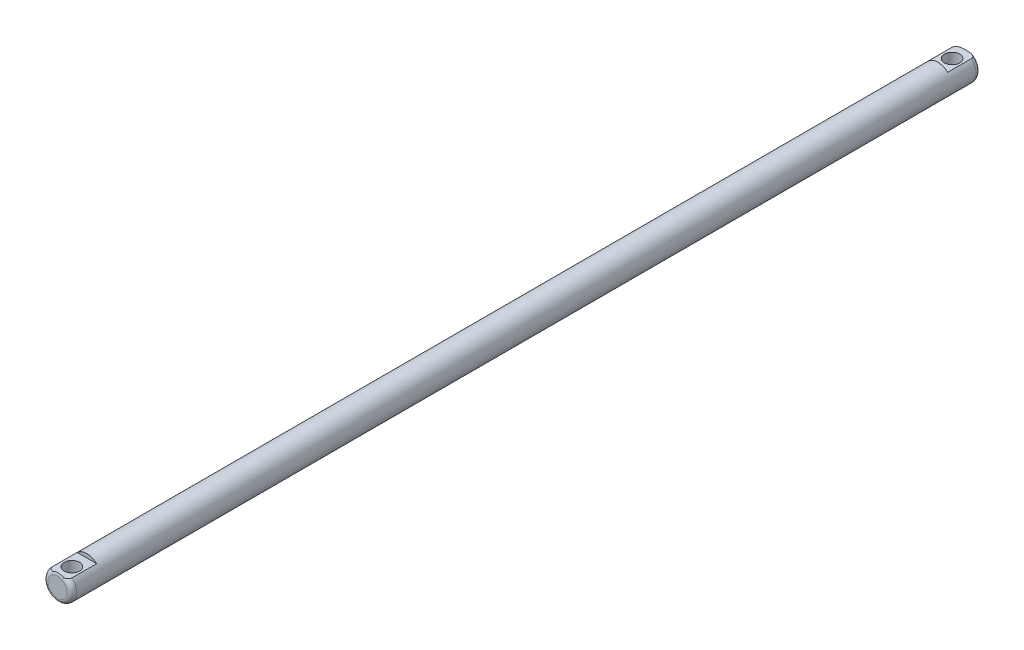
SolidWorks part; units mm, degrees
ref_plane "Front Plane" through (0, 0, 0) normal (0, 0, 1) x (1, 0, 0)
ref_plane "Top Plane" through (0, 0, 0) normal (0, 1, 0) x (1, 0, 0)
ref_plane "Right Plane" through (0, 0, 0) normal (1, 0, 0) x (0, 0, -1)
sketch "Sketch1" plane through (0, 0, 0) normal (0, 0, 1) x (1, 0, 0)
  circle A0 centre (-5.9113, 0) radius 1.5
extrude "Boss-Extrude1" add sketch "Sketch1" along normal blind 95
sketch "Sketch3" plane through (0, 0, 0) normal (0, 1, 0) x (1, 0, 0)
  line L0 (-4.4113, 0) -> (-7.4113, 0) construction
  line L1 (-7.4113, 0) -> (-7.4113, -95) construction
  line L2 (-7.4113, -95) -> (-4.4113, -95) construction
  circle A0 centre (-5.9113, -1.5) radius 0.8
  circle A1 centre (-5.9113, -93.5) radius 0.8
  dimension "D1" = 1.6
  dimension "D4" = 1.5
  dimension "D5" = 1.6
  dimension "D2" = 1.5
  dimension "D3" = 1.5
  dimension "D6" = 1.5
extrude "Cut-Extrude1" cut sketch "Sketch3" against normal blind 50 and the other way blind 50
fillet "Fillet1" radius 0.5 2 edges at (-4.4113, 0, 0) (-4.4113, 0, 95)
ref_plane "Plane1" through (0, 1.5, 0) normal (0, 1, 0) x (1, 0, 0)
sketch "Sketch4" plane through (0, 1.5, 0) normal (0, 1, 0) x (1, 0, 0)
  line L0 (-4.4113, -94.5) -> (-4.4113, -0.5) construction
  line L1 (-7.1613, -91.933) -> (-4.6613, -91.933)
  line L2 (-7.1613, -91.933) -> (-7.1613, -94.933)
  line L3 (-7.1613, -94.933) -> (-4.6613, -94.933)
  line L4 (-4.6613, -91.933) -> (-4.6613, -94.933)
  line L5 (-7.1613, 0.0158) -> (-4.6613, 0.0158)
  line L6 (-7.1613, 0.0158) -> (-7.1613, -2.9842)
  line L7 (-7.1613, -2.9842) -> (-4.6613, -2.9842)
  line L8 (-4.6613, 0.0158) -> (-4.6613, -2.9842)
  arc A0 (-4.9113, -95) -> (-4.4113, -94.5) centre (-4.9113, -94.5) ccw construction
  circle A1 centre (-5.9113, -1.5) radius 0.8 construction
  dimension "D1" = 3
  dimension "D2" = 2.5
  dimension "D3" = 0.25
  dimension "D4" = 3
  dimension "D5" = 2.5
  dimension "D6" = 0.25
  dimension "D7" = 1.5158
extrude "Cut-Extrude3" cut sketch "Sketch4" against normal blind 0.4
